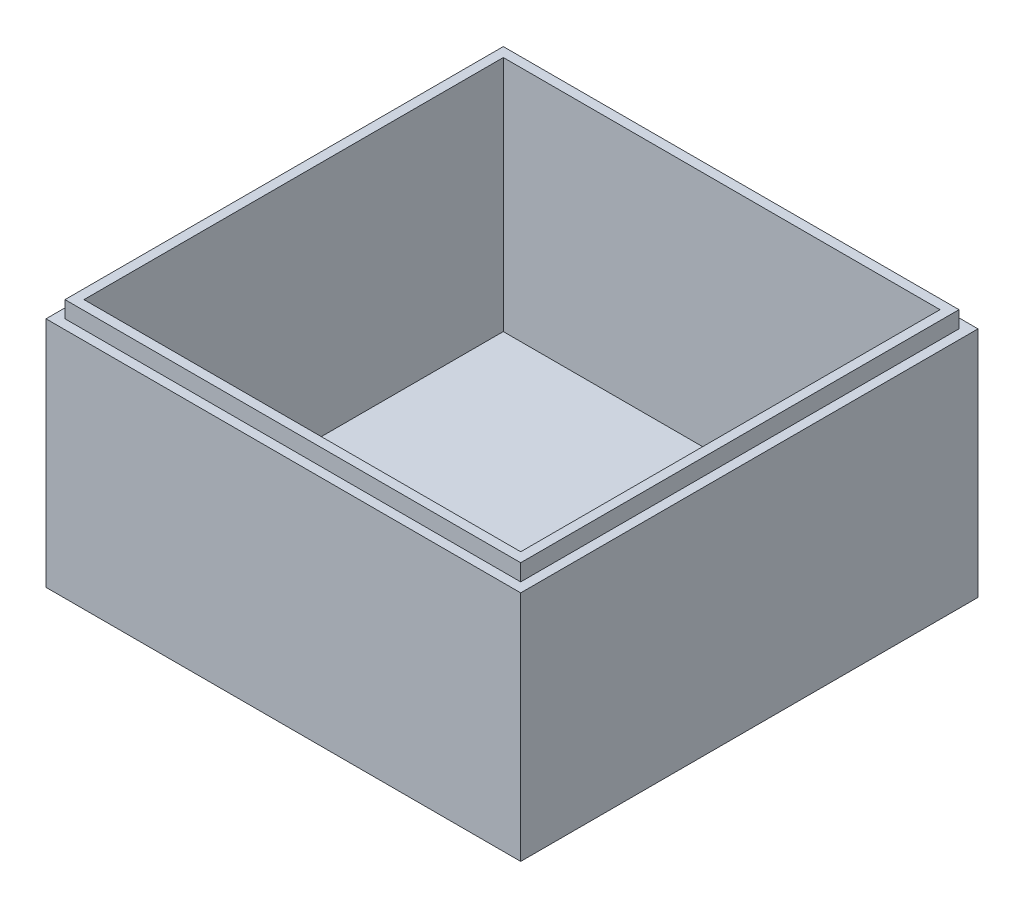
SolidWorks part; units mm, degrees
ref_plane "Front Plane" through (0, 0, 0) normal (0, 0, 1) x (1, 0, 0)
ref_plane "Top Plane" through (0, 0, 0) normal (0, 1, 0) x (1, 0, 0)
ref_plane "Right Plane" through (0, 0, 0) normal (1, 0, 0) x (0, 0, -1)
sketch "BatteryAndOuterWalls" plane through (0, 0, 0) normal (0, 1, 0) x (1, 0, 0)
  line L0 (30, -28.9) -> (30, 28.9)
  line L1 (27.6, -26.5) -> (-27.6, -26.5)
  line L2 (27.6, -26.5) -> (27.6, 26.5)
  line L3 (27.6, 26.5) -> (-27.6, 26.5)
  line L4 (-27.6, -26.5) -> (-27.6, 26.5)
  line L5 (27.6, -26.5) -> (-27.6, 26.5) construction
  line L6 (27.6, 26.5) -> (-27.6, -26.5) construction
  line L7 (30, 28.9) -> (-30, 28.9)
  line L8 (-30, -28.9) -> (-30, 28.9)
  line L9 (30, -28.9) -> (-30, -28.9)
  point P0 (0, 0)
  dimension "D1" = 55.2
  dimension "D2" = 53
  dimension "D4" = 60
  dimension "D5" = 57.8
  dimension "D3" = 2.4
extrude "Walls" add sketch "BatteryAndOuterWalls" along normal blind 30
sketch "SinkRim" plane through (0, 30, 0) normal (0, 1, 0) x (1, 0, 0)
  line L0 (-28.8, 27.7) -> (-28.8, -27.7)
  line L5 (-27.6, 26.5) -> (27.6, 26.5)
  line L6 (-27.6, 26.5) -> (-27.6, -26.5)
  line L7 (-27.6, -26.5) -> (27.6, -26.5)
  line L8 (27.6, 26.5) -> (27.6, -26.5)
  line L9 (-28.8, -27.7) -> (28.8, -27.7)
  line L10 (28.8, 27.7) -> (28.8, -27.7)
  line L11 (-28.8, 27.7) -> (28.8, 27.7)
  line L12 (-30, 28.9) -> (30, 28.9)
  line L13 (30, 28.9) -> (30, -28.9)
  line L14 (-30, -28.9) -> (30, -28.9)
  line L15 (-30, 28.9) -> (-30, -28.9)
  line M5 (-30, -28.9) -> (30, -28.9)
  line M6 (30, -28.9) -> (30, 28.9)
  line M7 (30, 28.9) -> (-30, 28.9)
  line M8 (-30, 28.9) -> (-30, -28.9)
  dimension "D1" = 1.2
  dimension "D2" = 1.2
sketch "Sketch2" plane through (0, 0, 0) normal (0, -1, 0) x (1, 0, 0)
  line L0 (-30, 28.9) -> (30, 28.9) construction
  line L5 (-30, 28.9) -> (30, 28.9)
  line L6 (-30, 28.9) -> (-30, -28.9)
  line L7 (-30, -28.9) -> (30, -28.9)
  line L8 (30, 28.9) -> (30, -28.9)
  line L9 (-30, -28.9) -> (-30, 28.9) construction
extrude "Bottom" add sketch "Sketch2" along normal blind 1.5
extrude "Top-Cut" cut sketch "SinkRim" against normal blind 2.1 contours L0 L11 L10 L9 M8 M5 M6 M7 region at (0, 30, -28.0669)
sketch "FrontRail" plane through (30, 0, 0) normal (1, 0, 0) x (0, 0, -1)
  line L0 (-28.9, 27.9) -> (-28.9, -1.5) construction
  line L1 (-26.5, 30) -> (26.5, 30)
  line L2 (-26.5, 30) -> (-26.5, 0)
  line L3 (-26.5, 0) -> (26.5, 0)
  line L4 (26.5, 30) -> (26.5, 0)
  line L5 (28.9, -1.5) -> (-28.9, -1.5) construction
  line L6 (28.9, 27.9) -> (28.9, -1.5) construction
  line L7 (27.7, 30) -> (-27.7, 30) construction
  line L8 (-26.5, 13) -> (-26.5, 14)
  line L9 (-26.5, 15) -> (-23.5, 15)
  line L10 (-26.5, 15) -> (-26.5, 14)
  line L11 (-26.5, 14) -> (-23.9, 14)
  line L12 (-23.5, 15) -> (-23.5, 14.4)
  line L29 (-26.5, 13) -> (-26.5, 14)
  line L30 (-26.5, 14) -> (-26.5, 13)
  arc A0 (-23.9, 14) -> (-26.5, 13) centre (-23.9, 10.12) ccw
  arc A1 (-23.5, 14.4) -> (-23.9, 14) centre (-23.9, 14.4) cw
  dimension "D1" = 2.4
  dimension "D2" = 1.5
  dimension "D3" = 2.4
  dimension "D4" = 0
  dimension "D5" = 14
  dimension "D7" = 3
  dimension "D8" = 1
  dimension "D9" = 15
extrude "Boss-Extrude2" add sketch "FrontRail" against normal blind 60 contours A0 L11 L2 | A1 L12 L9 L2 L11 region at (30, 14.5048, 25.0163) region at (30, 13.708, 25.8679)
